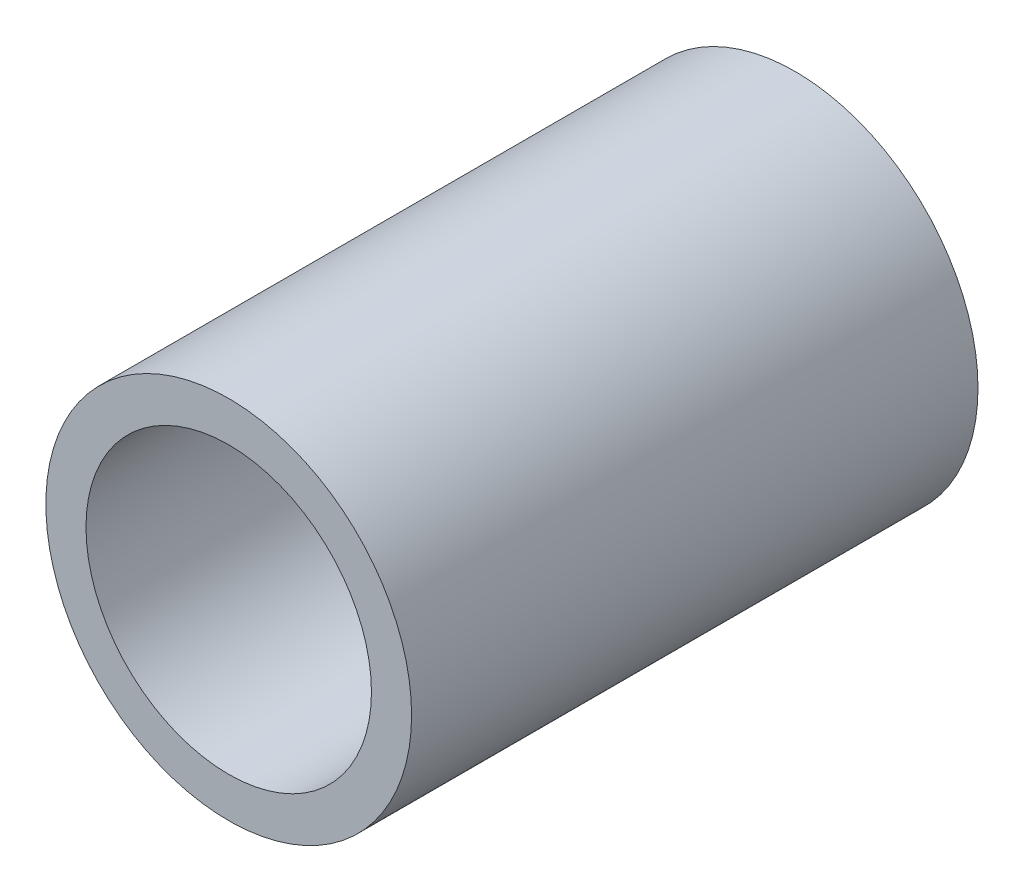
SolidWorks part; units mm, degrees
ref_plane "Front Plane" through (0, 0, 0) normal (0, 0, 1) x (1, 0, 0)
ref_plane "Top Plane" through (0, 0, 0) normal (0, 1, 0) x (1, 0, 0)
ref_plane "Right Plane" through (0, 0, 0) normal (1, 0, 0) x (0, 0, -1)
sketch "Sketch1" plane through (0, 0, 0) normal (1, 0, 0) x (0, 0, -1)
  line L0 (-11.1125, 7.1755) -> (-11.1125, 5.6007)
  line L1 (-11.1125, 5.6007) -> (11.1125, 5.6007)
  line L2 (11.1125, 5.6007) -> (11.1125, 7.1755)
  line L3 (11.1125, 7.1755) -> (-11.1125, 7.1755)
  line L4 (11.1125, 0) -> (-11.1125, 0) construction
revolve "Revolve1" add sketch "Sketch1" angle 360 about L4 reverse direction yes
ref_plane "bushing XY" through (0, 0, 0) normal (0, 0, 1) x (1, 0, 0)
ref_plane "bushing XZ" through (0, 0, 0) normal (0, -1, 0) x (-1, 0, 0)
ref_plane "bushing YZ" through (0, 0, 0) normal (1, 0, 0) x (0, 0, -1)
ref_axis "bushing X" through (-80.9, 0, 0) along (1, 0, 0)
ref_axis "bushing Y" through (0, -50, 0) along (0, 1, 0)
ref_axis "bushing Z" through (0, 0, 80.9) along (0, 0, -1)
sketch3d "bushing"
  point P0 (0, 0, 0)
ref_plane "id1 XY" through (0, 0, 0) normal (0, 0, 1) x (1, 0, 0)
ref_plane "id1 XZ" through (0, 0, 0) normal (0, -1, 0) x (-1, 0, 0)
ref_plane "id1 YZ" through (-5.6007, 0, 0) normal (1, 0, 0) x (0, 0, -1)
ref_axis "id1 X" through (-80.9, 0, 0) along (1, 0, 0)
ref_axis "id1 Y" through (-5.6007, -50, 0) along (0, 1, 0)
ref_axis "id1 Z" through (-5.6007, 0, 80.9) along (0, 0, -1)
sketch3d "id1"
  point P0 (-5.6007, 0, 0)
ref_plane "id2 XY" through (0, 0, 0) normal (0, 0, 1) x (1, 0, 0)
ref_plane "id2 XZ" through (0, 0, 0) normal (0, -1, 0) x (-1, 0, 0)
ref_plane "id2 YZ" through (5.6007, 0, 0) normal (1, 0, 0) x (0, 0, -1)
ref_axis "id2 X" through (-80.9, 0, 0) along (1, 0, 0)
ref_axis "id2 Y" through (5.6007, -50, 0) along (0, 1, 0)
ref_axis "id2 Z" through (5.6007, 0, 80.9) along (0, 0, -1)
sketch3d "id2"
  point P0 (5.6007, 0, 0)
ref_plane "id3 XY" through (0, 0, -11.1125) normal (0, 0, -1) x (-1, 0, 0)
ref_plane "id3 XZ" through (0, 0, 0) normal (-1, 0, 0) x (0, 0, 1)
ref_plane "id3 YZ" through (0, 0, 0) normal (0, 1, 0) x (1, 0, 0)
ref_axis "id3 X" through (0, -50, -11.1125) along (0, 1, 0)
ref_axis "id3 Y" through (-80.9, 0, -11.1125) along (1, 0, 0)
ref_axis "id3 Z" through (0, 0, -50) along (0, 0, 1)
sketch3d "id3"
  point P0 (0, 0, -11.1125)
ref_plane "id4 XY" through (0, 0, 11.1125) normal (0, 0, 1) x (1, 0, 0)
ref_plane "id4 XZ" through (0, 0, 0) normal (1, 0, 0) x (0, 0, -1)
ref_plane "id4 YZ" through (0, 0, 0) normal (0, 1, 0) x (1, 0, 0)
ref_axis "id4 X" through (0, -50, 11.1125) along (0, 1, 0)
ref_axis "id4 Y" through (80.9, 0, 11.1125) along (-1, 0, 0)
ref_axis "id4 Z" through (0, 0, 50) along (0, 0, -1)
sketch3d "id4"
  point P0 (0, 0, 11.1125)
